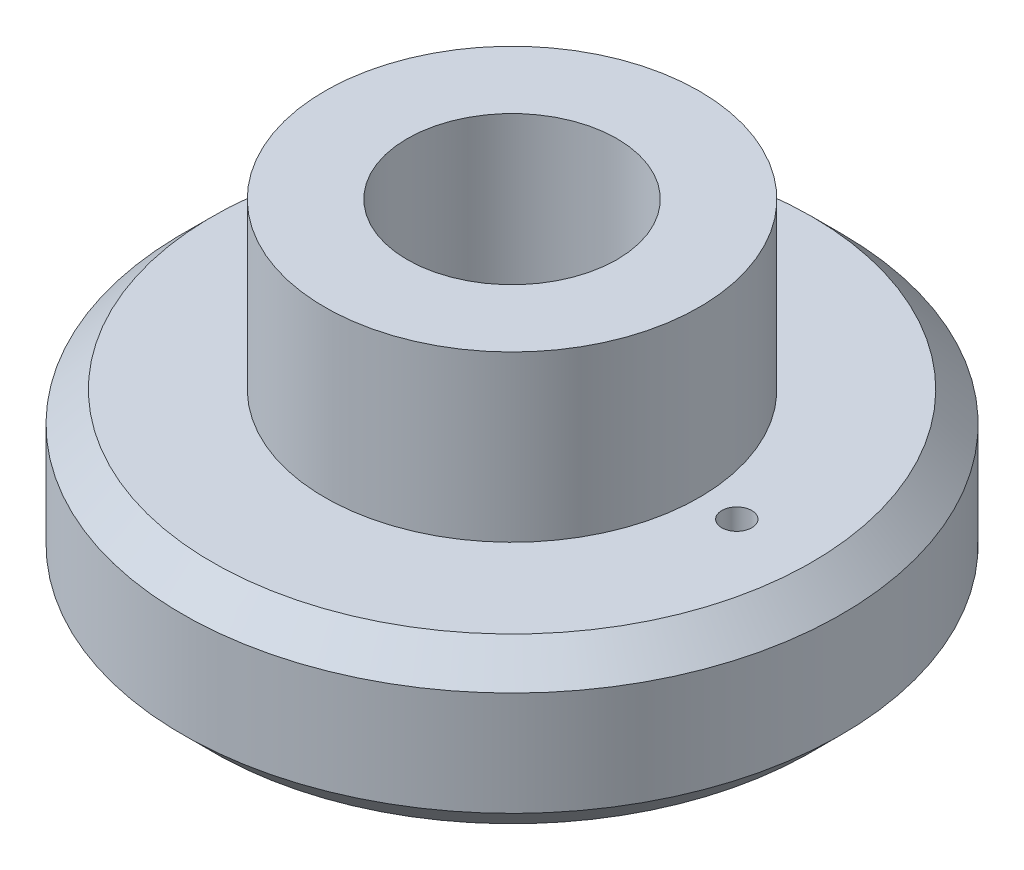
SolidWorks part; units mm, degrees
ref_plane "Front" through (0, 0, 0) normal (0, 0, 1) x (1, 0, 0)
ref_plane "Top" through (0, 0, 0) normal (0, 1, 0) x (1, 0, 0)
ref_plane "Right" through (0, 0, 0) normal (1, 0, 0) x (0, 0, -1)
sketch "Эскиз1" plane through (0, 0, 0) normal (0, 0, 1) x (1, 0, 0)
  line L0 (0, 0) -> (0, 6.9221) construction
  line L1 (7, 22) -> (7, 0)
  line L2 (7, 0) -> (17.5, 0)
  line L3 (17.5, 0) -> (17.5, 11)
  line L4 (17.5, 11) -> (12.5, 11)
  line L5 (12.5, 11) -> (12.5, 22)
  line L6 (12.5, 22) -> (7, 22)
  dimension "D1" = 35
  dimension "D2" = 14
  dimension "D3" = 11
  dimension "D4" = 11
  dimension "D5" = 25
revolve "Повернуть1" add sketch "Эскиз1" angle 360 about L0
sketch "Эскиз2" plane through (0, 0, 0) normal (0, 0, 1) x (1, 0, 0)
  line L3 (1.5, -27.4214) -> (-1.5, -27.4214)
  line L4 (1.5, -27.4214) -> (1.5, 27.4214)
  line L5 (1.5, 27.4214) -> (-1.5, 27.4214)
  line L6 (-1.5, -27.4214) -> (-1.5, 27.4214)
  line L7 (1.5, -27.4214) -> (-1.5, 27.4214) construction
  line L8 (1.5, 27.4214) -> (-1.5, -27.4214) construction
  point P0 (0, 0)
  dimension "D1" = 3
extrude "Вырез-Вытянуть1" [suppressed] cut sketch "Эскиз2" against normal blind 6.4
sketch "Эскиз3" plane through (0, 0, 0) normal (0, 0, 1) x (1, 0, 0)
  line L0 (0, 0) -> (0, 23.7771) construction
  line L1 (17.5, 0.0001) -> (17.5, 10.9999)
  line L2 (17.5, 0) -> (17.5, 11) construction
  line L3 (17.5, 10.9999) -> (20, 10.9999)
  line L6 (20, 10.9999) -> (22, 8.9999)
  line L7 (19.9561, 0.0001) -> (22, 2.044)
  line L8 (22, 2.044) -> (22, 8.9999)
  line L11 (19.9561, 0.0001) -> (17.5, 0.0001)
  line L12 (17.5, 11) -> (-17.5, 11) construction
  dimension "D1" = 0.0001
  dimension "D2" = 0.0001
  dimension "D3" = 44
revolve "Повернуть-Тонкостенный1" add sketch "Эскиз3" angle 360 about L0 wall 0.0001
sketch "Эскиз4" plane through (0, 11, 0) normal (0, 1, 0) x (1, 0, 0)
  circle A0 centre (-15, 0) radius 1
  circle A1 centre (15, 0) radius 1
  dimension "D3" = 2
  dimension "D4" = 2
  dimension "D1" = 15
  dimension "D2" = 15
extrude "Вырез-Вытянуть2" cut sketch "Эскиз4" against normal through all
